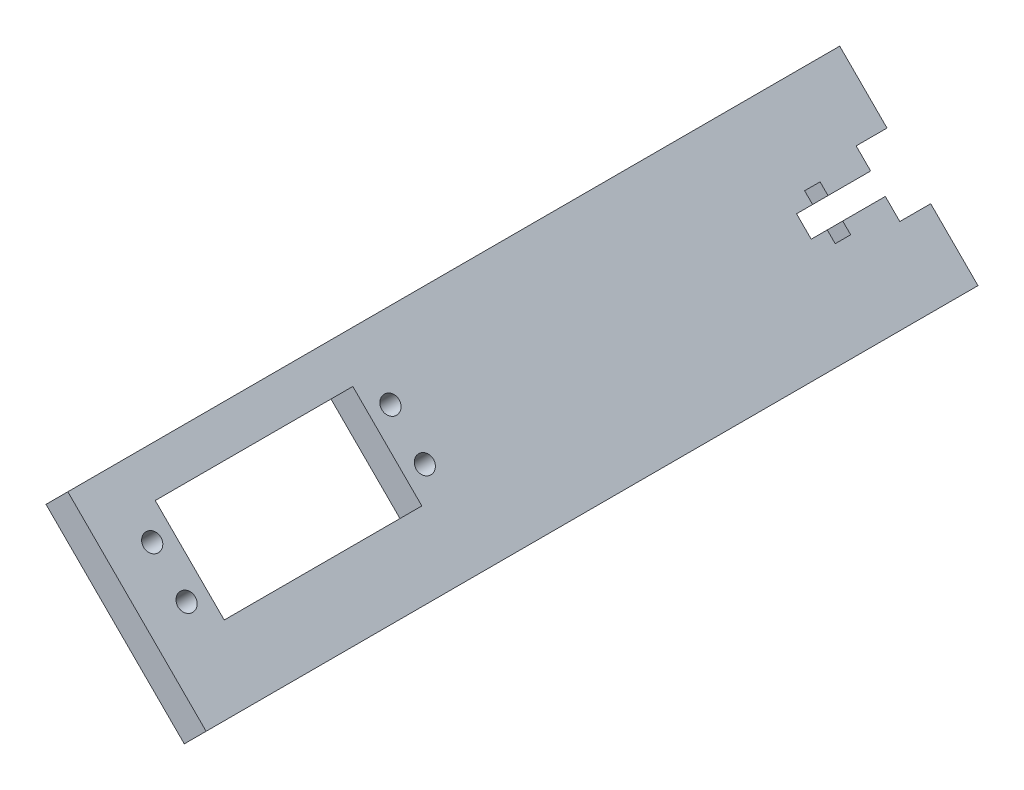
SolidWorks part; units mm, degrees
ref_plane "Front Plane" through (0, 0, 0) normal (0, 0, 1) x (1, 0, 0)
ref_plane "Top Plane" through (0, 0, 0) normal (0, 1, 0) x (1, 0, 0)
ref_plane "Right Plane" through (0, 0, 0) normal (1, 0, 0) x (0, 0, -1)
sketch "Sketch2" plane through (0, 0, 0) normal (0, 0, 1) x (1, 0, 0)
  line L0 (-62.1202, -135.0639) -> (-66.6103, -139.554)
  line L1 (-62.1202, -135.0639) -> (-33.676, -163.5081)
  line L2 (-66.6103, -139.554) -> (-38.1661, -167.9983)
  line L3 (-33.676, -163.5081) -> (-38.1661, -167.9983)
  line L4 (-66.6103, -139.554) -> (-56.8783, -149.286) construction
  line L5 (-52.3882, -144.7959) -> (-62.1202, -135.0639) construction
  line L6 (-38.1661, -167.9983) -> (-33.676, -163.5081) construction
  line L7 (-62.1202, -135.0639) -> (-66.6103, -139.554) construction
extrude "Boss-Extrude1" add sketch "Sketch2" along normal blind 152.4
sketch "Sketch3" plane through (-103.0822, -103.0822, 0) normal (-0.7071, -0.7071, 0) x (0, 0, 1)
  line L0 (0, -71.6921) -> (24.1393, -71.6921) construction
  line L1 (0, -51.579) -> (0, -91.8052) construction
  line B0 (0, -69.5585) -> (0, -73.8257)
  line B1 (11.938, -73.8257) -> (11.938, -76.1371)
  line B2 (11.938, -76.1371) -> (8.763, -76.1371)
  line B3 (8.763, -76.1371) -> (8.763, -73.8257)
  line B4 (8.763, -73.8257) -> (0, -73.8257)
  line B5 (11.938, -73.8257) -> (15.24, -73.8257)
  line B6 (15.24, -73.8257) -> (15.24, -69.5585)
  line B7 (11.938, -69.5585) -> (15.24, -69.5585)
  line B8 (8.763, -69.5585) -> (0, -69.5585)
  line B9 (8.763, -67.2471) -> (8.763, -69.5585)
  line B10 (11.938, -67.2471) -> (8.763, -67.2471)
  line B11 (11.938, -69.5585) -> (11.938, -67.2471)
sketch_block_instance "TSlot-1"
sketch_block "TSlot" parameters "D1"=3.302, "D2"=3.175
extrude "Cut-Extrude1" cut sketch "Sketch3" against normal through all
sketch "Sketch4" plane through (0, 0, 0) normal (0, 0, -1) x (-1, 0, 0)
  line L0 (66.6103, -139.554) -> (56.8783, -149.286) construction
  line L1 (56.8783, -149.286) -> (52.3882, -144.7959) construction
  line L2 (52.3882, -144.7959) -> (62.1202, -135.0639) construction
  line L3 (62.1202, -135.0639) -> (66.6103, -139.554) construction
  line L4 (33.676, -163.5081) -> (43.408, -153.7761) construction
  line L5 (43.408, -153.7761) -> (47.8981, -158.2663) construction
  line L6 (47.8981, -158.2663) -> (38.1661, -167.9983) construction
  line L7 (38.1661, -167.9983) -> (33.676, -163.5081) construction
  line L8 (66.6103, -139.554) -> (56.8783, -149.286)
  line L9 (56.8783, -149.286) -> (52.3882, -144.7959)
  line L10 (52.3882, -144.7959) -> (62.1202, -135.0639)
  line L11 (62.1202, -135.0639) -> (66.6103, -139.554)
  line L12 (33.676, -163.5081) -> (43.408, -153.7761)
  line L13 (43.408, -153.7761) -> (47.8981, -158.2663)
  line L14 (47.8981, -158.2663) -> (38.1661, -167.9983)
  line L15 (38.1661, -167.9983) -> (33.676, -163.5081)
extrude "Boss-Extrude2" add sketch "Sketch4" along normal blind 6.35
sketch "Sketch5" plane through (-98.592, -98.592, 0) normal (0.7071, 0.7071, 0) x (0, 0, -1)
  line L1 (-139.7, -59.0392) -> (-99.06, -59.0392)
  line L2 (-139.7, -59.0392) -> (-139.7, -79.1052)
  line L3 (-139.7, -79.1052) -> (-99.06, -79.1052)
  line L4 (-99.06, -59.0392) -> (-99.06, -79.1052)
  line L5 (-152.4, -91.8052) -> (-152.4, -51.579) construction
  line L6 (-130.8652, -59.0392) -> (-104.8465, -59.0392) construction
  line L7 (-104.8465, -79.1052) -> (-129.9845, -79.1052) construction
  line L8 (-130.8652, -59.0392) -> (-104.8465, -59.0392) construction
  line L9 (-104.8465, -79.1052) -> (-129.9845, -79.1052) construction
  dimension "D1" = 40.64
  dimension "D2" = 12.7
extrude "Cut-Extrude2" cut sketch "Sketch5" against normal through all
sketch "Sketch6" plane through (-98.592, -98.592, 0) normal (0.7071, 0.7071, 0) x (0, 0, -1)
  circle A8 centre (-143.88, -64.0722) radius 1.778
  circle A9 centre (-143.88, -74.0722) radius 1.778
  circle A10 centre (-94.88, -64.0722) radius 1.778
  circle A11 centre (-94.88, -74.0722) radius 1.778
extrude "Cut-Extrude3" cut sketch "Sketch6" against normal through all
